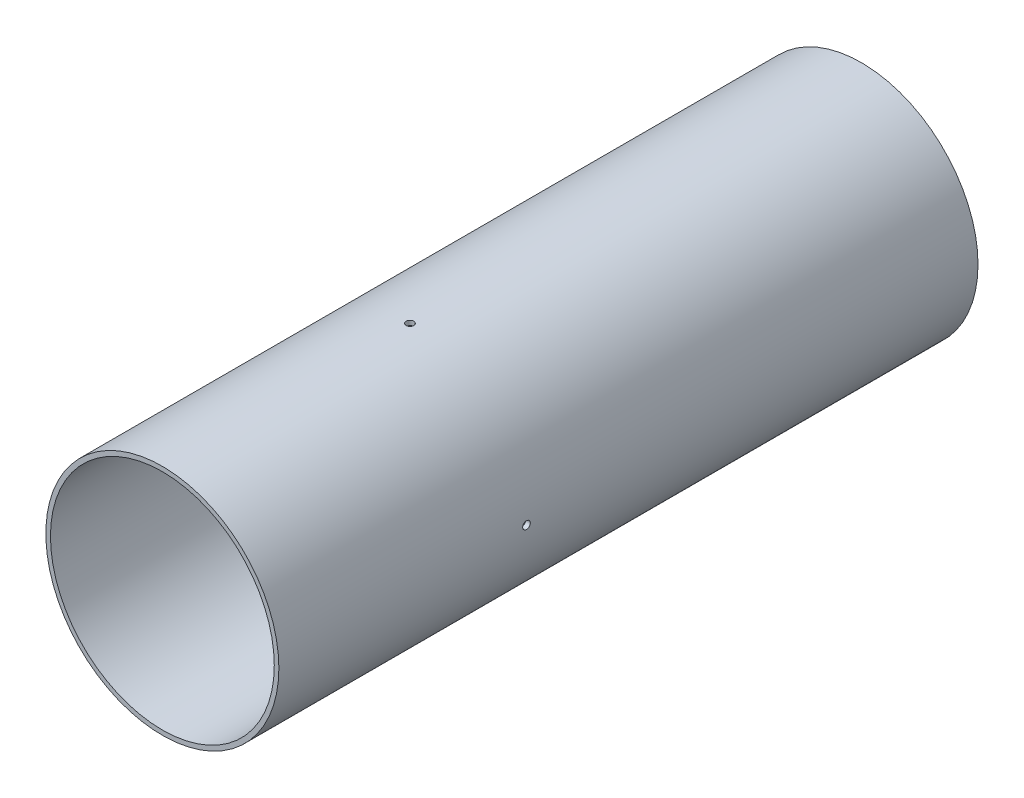
SolidWorks part; units mm, degrees
ref_plane "Front Plane" through (0, 0, 0) normal (0, 0, 1) x (1, 0, 0)
ref_plane "Top Plane" through (0, 0, 0) normal (0, 1, 0) x (1, 0, 0)
ref_plane "Right Plane" through (0, 0, 0) normal (1, 0, 0) x (0, 0, -1)
sketch "Sketch1" plane through (0, 0, 0) normal (0, 0, 1) x (1, 0, 0)
  circle A0 centre (0, 0) radius 50.8
  circle A1 centre (0, 0) radius 48.7934
  dimension "D1" = 101.6
  dimension "D2" = 2.0066
extrude "Boss-Extrude1" add sketch "Sketch1" along normal blind 304.8
ref_plane "Plane1" through (-50.8, 0, 0) normal (-1, 0, 0) x (0, 0, 1)
sketch "Sketch2" plane through (-50.8, 0, 0) normal (-1, 0, 0) x (0, 0, 1)
  line L0 (304.8, 0) -> (0, 0) construction
  line L1 (304.8, -50.8) -> (304.8, 50.8) construction
  line L2 (0, 50.8) -> (0, -50.8) construction
  circle A0 centre (196.85, 0) radius 1.651
  dimension "D1" = 107.95
  dimension "D2" = 3.302
extrude "Cut-Extrude1" cut sketch "Sketch2" against normal up to next
pattern_circular "CirPattern1" count 4 over 360 about axis through (0, 0, 304.8) along (0, 0, -1) of "Cut-Extrude1" reverse direction yes
